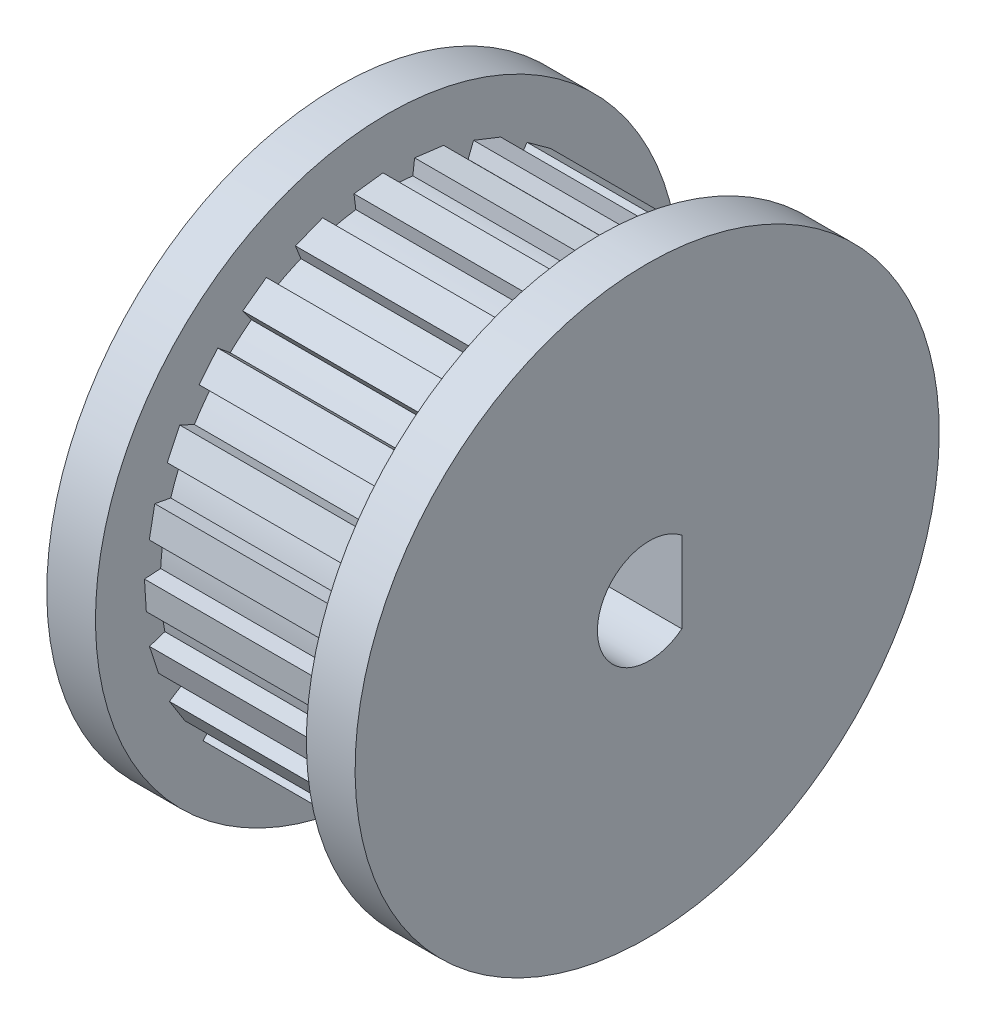
SolidWorks part; units mm, degrees
material "PLA"
ref_plane "Top" through (0, 0, 0) normal (0, 0, 1) x (1, 0, 0)
ref_plane "Right" through (0, 0, 0) normal (0, 1, 0) x (1, 0, 0)
ref_plane "Front" through (0, 0, 0) normal (1, 0, 0) x (0, 0, -1)
ref_plane "Plane1" through (-20.8257, 0, 0) normal (1, 0, 0) x (0, 0, -1)
ref_axis "Axis1" through (-2.1732, 75.715, -263.3647) along (-1, 0, 0)
ref_plane "Plane2" through (0, 158.0168, -65.8403) normal (0, 0.9231, -0.3846) x (1, 0, 0)
sketch "Sketch1" plane through (0, 158.0168, -65.8403) normal (0, 0.9231, -0.3846) x (1, 0, 0)
  line L0 (-11.0757, 213.9112) -> (-21.0757, 213.9112) construction
  line L3 (-11.0757, 212.4847) -> (-11.0757, 215.3378) construction
  line L4 (-21.0757, 212.4847) -> (-21.0757, 215.3378) construction
  line L5 (-20.0757, 213.9112) -> (-10.5757, 213.9112)
  line L8 (-21.0757, 213.9112) -> (-21.0757, 214.4778) construction
  line L9 (-21.0757, 214.4778) -> (-21.0757, 215.3378) construction
  line L10 (-20.0757, 213.9112) -> (-20.0757, 204.9112)
  line L11 (-20.0757, 204.9112) -> (-18.5757, 204.9112)
  line L12 (-18.5757, 204.9112) -> (-18.5757, 206.9112)
  line L13 (-18.5757, 206.9112) -> (-12.0757, 206.9112)
  line L14 (-12.0757, 206.9112) -> (-12.0757, 204.9112)
  line L15 (-12.0757, 204.9112) -> (-10.5757, 204.9112)
  line L16 (-10.5757, 204.9112) -> (-10.5757, 213.9112)
  dimension "D1" = 1
  dimension "D2" = 2
  dimension "D3" = 7
  dimension "D4" = 1.5
  dimension "D5" = 1.5
  dimension "D6" = 6.5
revolve "Revolve1" add sketch "Sketch1" angle 360 about L0
sketch "Sketch2" plane through (-18.5757, 0, 0) normal (1, 0, 0) x (0, 0, -1)
  line L0 (263.2969, 75.7432) -> (263.2969, 55.5748) construction
  line L1 (263.3969, 68.744) -> (263.3969, 68.2891)
  line L2 (263.3969, 68.2891) -> (262.4969, 68.2891)
  line L3 (262.4969, 68.2891) -> (262.4969, 68.7891)
  line L4 (261.6531, 68.939) -> (261.54, 68.4984)
  line L5 (261.54, 68.4984) -> (260.6682, 68.7222)
  line L6 (260.6682, 68.7222) -> (260.7926, 69.2065)
  line L7 (260.0126, 69.5615) -> (259.7934, 69.163)
  line L8 (259.7934, 69.163) -> (259.0048, 69.5965)
  line L9 (259.0048, 69.5965) -> (259.2456, 70.0347)
  line L10 (258.5784, 70.5725) -> (258.2671, 70.241)
  line L11 (258.2671, 70.241) -> (257.611, 70.857)
  line L12 (257.611, 70.857) -> (257.9533, 71.2215)
  line L13 (257.4408, 71.9084) -> (257.0567, 71.6647)
  line L14 (257.0567, 71.6647) -> (256.5745, 72.4246)
  line L15 (256.5745, 72.4246) -> (256.9966, 72.6925)
  line L16 (256.671, 73.4852) -> (256.2385, 73.3447)
  line L17 (256.2385, 73.3447) -> (255.9603, 74.2006)
  line L18 (255.9603, 74.2006) -> (256.4359, 74.3551)
  line L19 (256.3177, 75.2039) -> (255.8637, 75.1754)
  line L20 (255.8637, 75.1754) -> (255.8072, 76.0736)
  line L21 (255.8072, 76.0736) -> (256.3062, 76.105)
  line L22 (256.4028, 76.9565) -> (255.956, 77.0418)
  line L23 (255.956, 77.0418) -> (256.1247, 77.9258)
  line L24 (256.1247, 77.9258) -> (256.6158, 77.8321)
  line L25 (256.9211, 78.6329) -> (256.5096, 78.8266)
  line L26 (256.5096, 78.8266) -> (256.8928, 79.6409)
  line L27 (256.8928, 79.6409) -> (257.3452, 79.428)
  line L28 (257.8401, 80.1277) -> (257.4896, 80.4176)
  line L29 (257.4896, 80.4176) -> (258.0633, 81.1111)
  line L30 (258.0633, 81.1111) -> (258.4485, 80.7924)
  line L31 (259.1019, 81.347) -> (258.8345, 81.715)
  line L32 (258.8345, 81.715) -> (259.5626, 82.244)
  line L33 (259.5626, 82.244) -> (259.8565, 81.8395)
  line L34 (260.6273, 82.2142) -> (260.4598, 82.6371)
  line L35 (260.4598, 82.6371) -> (261.2966, 82.9684)
  line L36 (261.2966, 82.9684) -> (261.4807, 82.5035)
  line L37 (262.3204, 82.6748) -> (262.2634, 83.1261)
  line L38 (262.2634, 83.1261) -> (263.1563, 83.2389)
  line L39 (263.1563, 83.2389) -> (263.219, 82.7428)
  line L40 (264.0749, 82.6999) -> (264.1319, 83.1511)
  line L41 (264.1319, 83.1511) -> (265.0248, 83.0383)
  line L42 (265.0248, 83.0383) -> (264.9621, 82.5423)
  line L43 (265.7805, 82.2878) -> (265.9479, 82.7107)
  line L44 (265.9479, 82.7107) -> (266.7847, 82.3794)
  line L45 (266.7847, 82.3794) -> (266.6007, 81.9145)
  line L46 (267.33, 81.4646) -> (267.5974, 81.8325)
  line L47 (267.5974, 81.8325) -> (268.3255, 81.3035)
  line L48 (268.3255, 81.3035) -> (268.0316, 80.899)
  line L49 (268.6262, 80.2818) -> (268.9766, 80.5717)
  line L50 (268.9766, 80.5717) -> (269.5503, 79.8783)
  line L51 (269.5503, 79.8783) -> (269.1651, 79.5596)
  line L52 (269.5874, 78.8139) -> (269.999, 79.0075)
  line L53 (269.999, 79.0075) -> (270.3822, 78.1932)
  line L54 (270.3822, 78.1932) -> (269.9298, 77.9803)
  line L55 (270.1534, 77.153) -> (270.6002, 77.2382)
  line L56 (270.6002, 77.2382) -> (270.7689, 76.3542)
  line L57 (270.7689, 76.3542) -> (270.2777, 76.2605)
  line L58 (270.2886, 75.4036) -> (270.7426, 75.375)
  line L59 (270.7426, 75.375) -> (270.6861, 74.4768)
  line L60 (270.6861, 74.4768) -> (270.187, 74.5082)
  line L61 (269.9845, 73.6754) -> (270.4171, 73.5349)
  line L62 (270.4171, 73.5349) -> (270.139, 72.6789)
  line L63 (270.139, 72.6789) -> (269.6634, 72.8334)
  line L64 (269.2601, 72.0773) -> (269.6442, 71.8335)
  line L65 (269.6442, 71.8335) -> (269.1619, 71.0736)
  line L66 (269.1619, 71.0736) -> (268.7398, 71.3416)
  line L67 (268.1611, 70.7094) -> (268.4725, 70.3779)
  line L68 (268.4725, 70.3779) -> (267.8164, 69.7618)
  line L69 (267.8164, 69.7618) -> (267.4741, 70.1263)
  line L70 (266.7564, 69.6579) -> (266.9756, 69.2593)
  line L71 (266.9756, 69.2593) -> (266.1869, 68.8257)
  line L72 (266.1869, 68.8257) -> (265.946, 69.2639)
  line L73 (265.1344, 68.9887) -> (265.2475, 68.5482)
  line L74 (265.2475, 68.5482) -> (264.3758, 68.3243)
  line L75 (264.3758, 68.3243) -> (264.2514, 68.8086)
  arc A0 (262.4969, 68.7891) -> (263.3969, 68.744) centre (263.2969, 75.7432) ccw
  circle A1 centre (263.2969, 75.7432) radius 7 construction
  arc A2 (260.7926, 69.2065) -> (261.6531, 68.939) centre (263.2969, 75.7432) ccw
  arc A3 (259.2456, 70.0347) -> (260.0126, 69.5615) centre (263.2969, 75.7432) ccw
  arc A4 (257.9533, 71.2215) -> (258.5784, 70.5725) centre (263.2969, 75.7432) ccw
  arc A5 (256.9966, 72.6925) -> (257.4408, 71.9084) centre (263.2969, 75.7432) ccw
  arc A6 (256.4359, 74.3551) -> (256.671, 73.4852) centre (263.2969, 75.7432) ccw
  arc A7 (256.3062, 76.105) -> (256.3177, 75.2039) centre (263.2969, 75.7432) ccw
  arc A8 (256.6158, 77.8321) -> (256.4028, 76.9565) centre (263.2969, 75.7432) ccw
  arc A9 (257.3452, 79.428) -> (256.9211, 78.6329) centre (263.2969, 75.7432) ccw
  arc A10 (258.4485, 80.7924) -> (257.8401, 80.1277) centre (263.2969, 75.7432) ccw
  arc A11 (259.8565, 81.8395) -> (259.1019, 81.347) centre (263.2969, 75.7432) ccw
  arc A12 (261.4807, 82.5035) -> (260.6273, 82.2142) centre (263.2969, 75.7432) ccw
  arc A13 (263.219, 82.7428) -> (262.3204, 82.6748) centre (263.2969, 75.7432) ccw
  arc A14 (264.9621, 82.5423) -> (264.0749, 82.6999) centre (263.2969, 75.7432) ccw
  arc A15 (266.6007, 81.9145) -> (265.7805, 82.2878) centre (263.2969, 75.7432) ccw
  arc A16 (268.0316, 80.899) -> (267.33, 81.4646) centre (263.2969, 75.7432) ccw
  arc A17 (269.1651, 79.5596) -> (268.6262, 80.2818) centre (263.2969, 75.7432) ccw
  arc A18 (269.9298, 77.9803) -> (269.5874, 78.8139) centre (263.2969, 75.7432) ccw
  arc A19 (270.2777, 76.2605) -> (270.1534, 77.153) centre (263.2969, 75.7432) ccw
  arc A20 (270.187, 74.5082) -> (270.2886, 75.4036) centre (263.2969, 75.7432) ccw
  arc A21 (269.6634, 72.8334) -> (269.9845, 73.6754) centre (263.2969, 75.7432) ccw
  arc A22 (268.7398, 71.3416) -> (269.2601, 72.0773) centre (263.2969, 75.7432) ccw
  arc A23 (267.4741, 70.1263) -> (268.1611, 70.7094) centre (263.2969, 75.7432) ccw
  arc A24 (265.946, 69.2639) -> (266.7564, 69.6579) centre (263.2969, 75.7432) ccw
  arc A25 (264.2514, 68.8086) -> (265.1344, 68.9887) centre (263.2969, 75.7432) ccw
  point P127 (263.2969, 75.7432)
  dimension "D1" = 0.1
  dimension "D2" = 0.8
  dimension "D3" = 0.5
  dimension "D4" = 25
extrude "Boss-Extrude1" add sketch "Sketch2" along normal up to surface (6.5 mm away) up to face at (-12.0757, 84.7432, -263.2969)
sketch "Sketch3" plane through (-10.5757, 0, 0) normal (1, 0, 0) x (0, 0, -1)
  line L0 (264.3647, 74.466) -> (264.3647, 76.964)
  line L2 (264.3647, 76.833) -> (264.3647, 74.597) construction
  arc A0 (264.3647, 76.964) -> (264.3647, 74.466) centre (263.3647, 75.715) ccw
  dimension "D1" = 3.2
extrude "Cut-Extrude1" cut sketch "Sketch3" against normal up to surface (9.5 mm away) up to face at (-20.0757, 84.7432, -263.2969)
